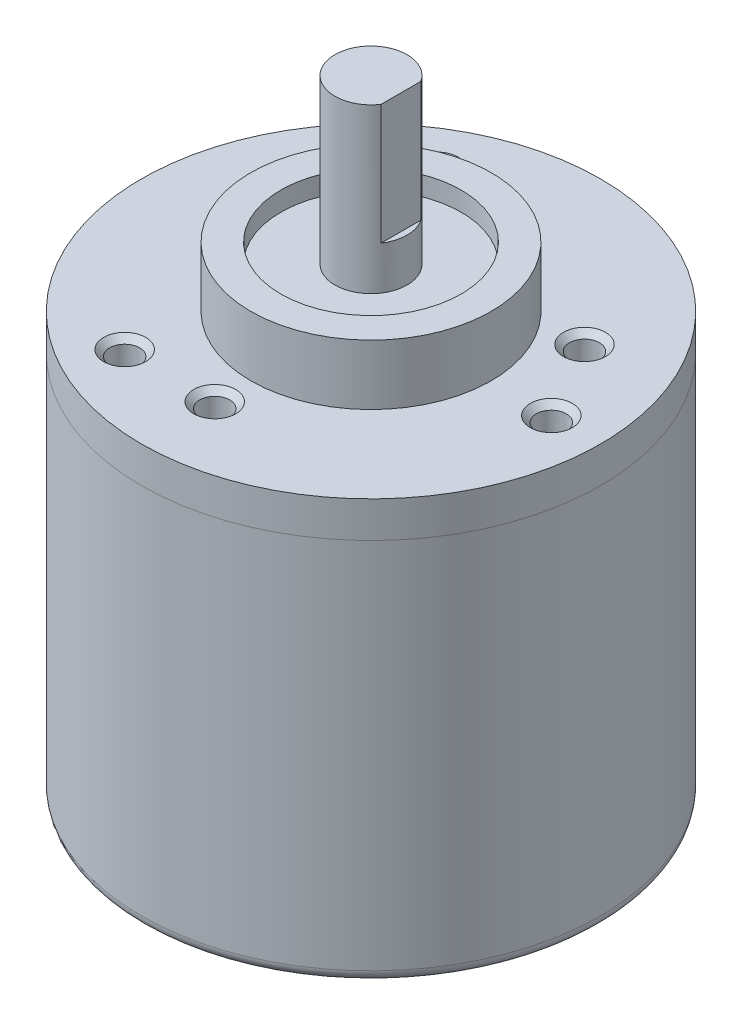
SolidWorks part; units mm, degrees
ref_plane "Front Plane" through (0, 0, 0) normal (0, 0, 1) x (1, 0, 0)
ref_plane "Top Plane" through (0, 0, 0) normal (0, 1, 0) x (1, 0, 0)
ref_plane "Right Plane" through (0, 0, 0) normal (1, 0, 0) x (0, 0, -1)
sketch "Sketch1" plane through (0, 0, 0) normal (0, 1, 0) x (1, 0, 0)
  circle A0 centre (0, 0) radius 19.1
  dimension "D1" = 38.2
extrude "Boss-Extrude1" add sketch "Sketch1" along normal blind 32
sketch "Sketch3" plane through (0, 32, 0) normal (0, 1, 0) x (1, 0, 0)
  line L0 (15, 0) -> (0, 0) construction
  line L1 (0, 0) -> (-7.5, 12.9904) construction
  line L2 (0, 0) -> (-7.5, -12.9904) construction
  line L3 (0, -13) -> (0, 0) construction
  line L4 (0, 0) -> (-11.2583, 6.5) construction
  line L5 (0, 0) -> (11.2583, 6.5) construction
  circle A0 centre (0, 0) radius 19.1
  circle A1 centre (0, 0) radius 19.1 construction
  circle A2 centre (0, 0) radius 13
  circle A3 centre (0, 0) radius 15
  circle A4 centre (15, 0) radius 1.25
  circle A5 centre (-7.5, -12.9904) radius 1.25
  circle A6 centre (-7.5, 12.9904) radius 1.25
  circle A7 centre (11.2583, 6.5) radius 1.25
  circle A8 centre (0, -13) radius 1.25
  circle A9 centre (-11.2583, 6.5) radius 1.25
  circle M1 centre (0, 0) radius 19.1
  dimension "D1" = 26
  dimension "D2" = 30
  dimension "D5" = 2.5
  dimension "D3" = 120
  dimension "D4" = 120
  dimension "D6" = 120
  dimension "D7" = 120
  dimension "D8" = 7.5
fillet "Fillet1" radius 1 1 edges at (0, 0, 19.1)
extrude "Boss-Extrude6" add sketch "Sketch3" along normal blind 3 separate body contours A6 A3 A4 A5 M1 | A6 A3 A5 A4 A9 A2 A7 A8 | A9 A2 A8 A7 region at (-18.5598, 32, 0) region at (0, 32, 0) region at (13.3261, 32, 0)
sketch "Sketch5" plane through (0, 35, 0) normal (0, 1, 0) x (1, 0, 0)
  circle A0 centre (0, 0) radius 10
  dimension "D1" = 20
extrude "Boss-Extrude7" add sketch "Sketch5" along normal blind 5
sketch "Sketch7" plane through (0, 40, 0) normal (0, 1, 0) x (1, 0, 0)
  circle A0 centre (0, 0) radius 7.5
  dimension "D1" = 15
extrude "Cut-Extrude1" cut sketch "Sketch7" against normal blind 1.6
sketch "Sketch8" plane through (0, 38.4, 0) normal (0, 1, 0) x (1, 0, 0)
  line L0 (2.5, 1.6583) -> (2.5, -1.6583)
  circle A0 centre (0, 0) radius 3
  dimension "D1" = 6
  dimension "D2" = 2.5
extrude "Boss-Extrude9" add sketch "Sketch8" along normal offset from surface (13.6 mm away) 12 contours L0 A0 region at (-0.112, 38.4, 0) up to face at (0, 40, 7.5) offset beyond the face yes
extrude "Boss-Extrude10" add sketch "Sketch8<3>" along normal offset from surface (3.6 mm away) 10 contours A0 up to face at (-0.25, 52, 0)
sketch "Sketch8<3>" plane through (0, 38.4, 0) normal (0, 1, 0) x (1, 0, 0) same geometry as "Sketch8"
chamfer "Chamfer1" distance 0.5 angle 45 6 edges at (-7.5, 35, -11.7404) (-11.2583, 35, -5.25) (-7.5, 35, 14.2404) (0, 35, 14.25) (15, 35, 1.25) (11.2583, 35, -5.25)
